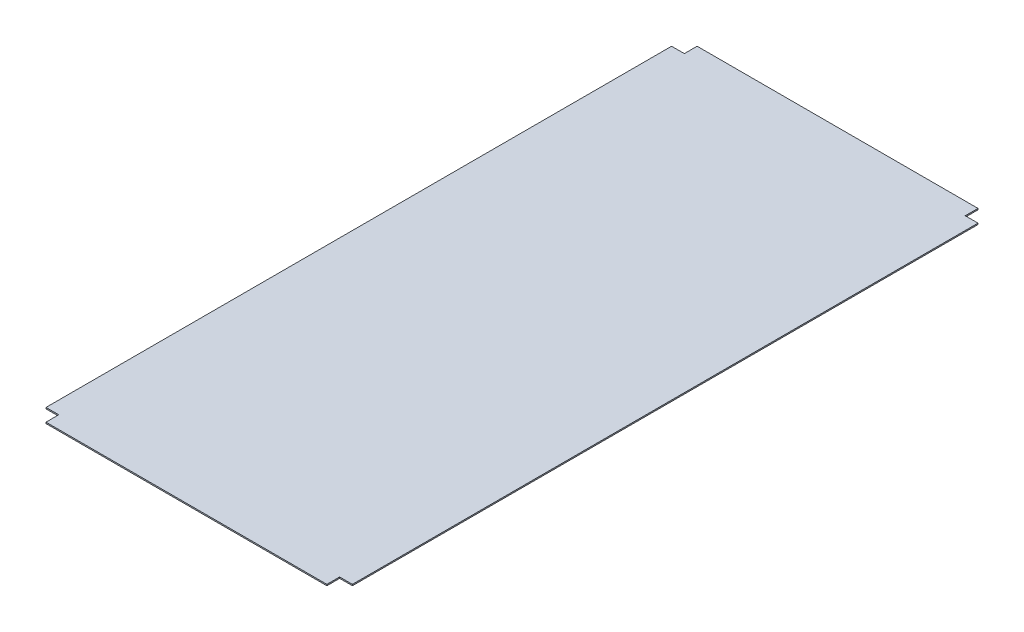
SolidWorks part; units mm, degrees
ref_plane "Alzado" through (0, 0, 0) normal (0, 0, 1) x (1, 0, 0)
ref_plane "Planta" through (0, 0, 0) normal (0, 1, 0) x (1, 0, 0)
ref_plane "Vista lateral" through (0, 0, 0) normal (1, 0, 0) x (0, 0, -1)
sketch "Croquis1" plane through (0, 0, 0) normal (0, 1, 0) x (1, 0, 0)
  line L1 (360, -765) -> (-360, -765)
  line L2 (360, -765) -> (360, 765)
  line L3 (360, 765) -> (-360, 765)
  line L4 (-360, -765) -> (-360, 765)
  line L5 (360, -765) -> (-360, 765) construction
  line L6 (360, 765) -> (-360, -765) construction
  point P0 (0, 0)
  dimension "D1" = 1530
  dimension "D2" = 720
extrude "Saliente-Extruir1" add sketch "Croquis1" along normal blind 3 contours L4 L3 L2 L1
sketch "Croquis2" plane through (0, 3, 0) normal (0, 1, 0) x (1, 0, 0)
  line L1 (-360, 765) -> (-330, 765)
  line L2 (-360, 765) -> (-360, 735)
  line L3 (-360, 735) -> (-330, 735)
  line L4 (-330, 765) -> (-330, 735)
  line L5 (360, 765) -> (330, 765)
  line L6 (360, 765) -> (360, 735)
  line L7 (360, 735) -> (330, 735)
  line L8 (330, 765) -> (330, 735)
  line L9 (360, -765) -> (330, -765)
  line L10 (360, -765) -> (360, -735)
  line L11 (360, -735) -> (330, -735)
  line L12 (330, -765) -> (330, -735)
  line L13 (-360, -765) -> (-330, -765)
  line L14 (-360, -765) -> (-360, -735)
  line L15 (-360, -735) -> (-330, -735)
  line L16 (-330, -765) -> (-330, -735)
  dimension "D1" = 30
extrude "Cortar-Extruir1" cut sketch "Croquis2" against normal through all
